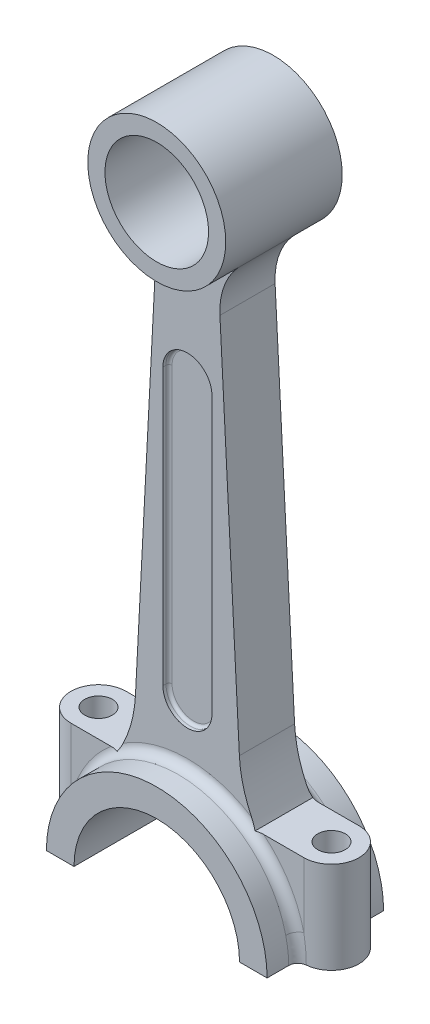
SolidWorks part; units mm, degrees
ref_plane "Front Plane" through (0, 0, 0) normal (0, 0, 1) x (1, 0, 0)
ref_plane "Top Plane" through (0, 0, 0) normal (0, 1, 0) x (1, 0, 0)
ref_plane "Right Plane" through (0, 0, 0) normal (1, 0, 0) x (0, 0, -1)
sketch "Sketch1" plane through (0, 0, 0) normal (0, 0, 1) x (1, 0, 0)
  line L0 (0, 0) -> (0, -201.2) construction
  line L1 (-10, -20.1556) -> (-17.8497, -169.9368)
  line L2 (10, -20.1556) -> (17.8497, -169.9368)
  line L3 (-36, -201.2) -> (-27, -201.2)
  line L4 (27, -201.2) -> (36, -201.2)
  circle A0 centre (0, 0) radius 22.5
  circle A1 centre (0, 0) radius 16.9
  arc A2 (36, -201.2) -> (-36, -201.2) centre (0, -201.2) ccw
  arc A3 (27, -201.2) -> (-27, -201.2) centre (0, -201.2) ccw
  dimension "D1" = 45
  dimension "D2" = 33.8
  dimension "D3" = 72
  dimension "D4" = 54
  dimension "D5" = 201.2
  dimension "D6" = 20
  dimension "D7" = 6
extrude "Boss-Extrude1" add sketch "Sketch1" along normal mid plane 38 contours A1 A0 | A2 A3 | L4 A2 L3 A3 region at (-11.5231, 18.5805, 0) region at (0, -166.005, 0)
extrude "Boss-Extrude2" add sketch "Sketch1<4>" along normal mid plane 18 contours L0 A0 L1 A2 | A0 L0 A2 L2 region at (7.1843, -100.8455, 0) region at (-7.1843, -100.8455, 0)
sketch "Sketch1<4>" plane through (0, 0, 0) normal (0, 0, 1) x (1, 0, 0) same geometry as "Sketch1"
sketch "Sketch2" plane through (0, 0, 9) normal (0, 0, 1) x (1, 0, 0)
  line L0 (0, 0) -> (0, -201.2) construction
  line L1 (0, -55.6) -> (0, -145.6) construction
  line L2 (8, -55.6) -> (8, -145.6)
  line L3 (-8, -55.6) -> (-8, -145.6)
  arc A0 (8, -55.6) -> (-8, -55.6) centre (0, -55.6) ccw
  arc A1 (-8, -145.6) -> (8, -145.6) centre (0, -145.6) ccw
  point P6 (0, -100.6)
  dimension "D2" = 8
  dimension "D1" = 90
extrude "Cut-Extrude1" cut sketch "Sketch2" against normal mid plane 4
mirror "Mirror1" about plane through (0, 0, 0) normal (0, 0, 1) of "Cut-Extrude1"
fillet "Fillet1" radius 1 8 edges at (-8, -100.6, -9) (0, -153.6, -9) (8, -100.6, -9) (8, -100.6, 7) (0, -153.6, 7) (-8, -100.6, 7) (0, -47.6, -9) (0, -47.6, 7)
fillet "Fillet2" radius 40 2 edges at (17.8497, -169.9368, 0) (-17.8497, -169.9368, 0)
fillet "Fillet3" radius 22.5 2 edges at (10, -20.1556, 0) (-10, -20.1556, 0)
ref_plane "Plane1" through (0, -171.2, 0) normal (0, -1, 0) x (-1, 0, 0)
sketch "Sketch3" plane through (0, -171.2, 0) normal (0, -1, 0) x (-1, 0, 0)
  line L0 (38, 0) -> (-38, 0) construction
  line L1 (38, -9) -> (-38, -9)
  line L2 (38, 9) -> (-38, 9)
  arc A0 (38, -9) -> (38, 9) centre (38, 0) ccw
  arc A1 (-38, 9) -> (-38, -9) centre (-38, 0) ccw
  point P2 (0, 0)
  dimension "D2" = 9
  dimension "D1" = 76
extrude "Boss-Extrude3" add sketch "Sketch3" along normal up to surface (30 mm away) up to face at (-31.5, -201.2, 0)
sketch "Sketch4" plane through (0, 0, 9) normal (0, 0, 1) x (1, 0, 0)
  line L0 (-27, -201.2) -> (27, -201.2) construction
  line L1 (-27, -201.2) -> (27, -201.2)
  arc A0 (-27, -201.2) -> (27, -201.2) centre (0, -201.2) cw
  arc A1 (27, -201.2) -> (-27, -201.2) centre (0, -201.2) ccw construction
extrude "Cut-Extrude4" cut sketch "Sketch4" against normal through all
sketch "Sketch5" plane through (0, -171.2, 0) normal (0, -1, 0) x (-1, 0, 0)
  circle A0 centre (-38, 0) radius 4.5
  circle A1 centre (38, 0) radius 4.5
  dimension "D1" = 9
  dimension "D2" = 9
extrude "Cut-Extrude5" cut sketch "Sketch5" along normal through all
fillet "Fillet4" radius 3 2 edges at (0, -165.2, -9) (0, -165.2, 9)
